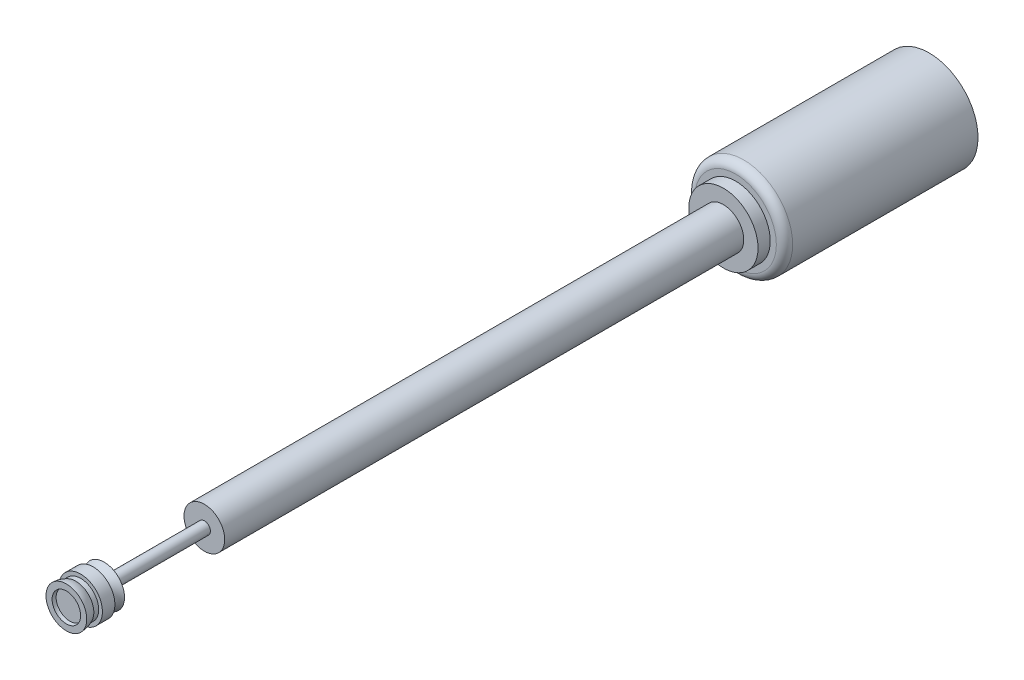
SolidWorks part; units mm, degrees
ref_plane "Front Plane" through (0, 0, 0) normal (0, 0, 1) x (1, 0, 0)
ref_plane "Top Plane" through (0, 0, 0) normal (0, 1, 0) x (1, 0, 0)
ref_plane "Right Plane" through (0, 0, 0) normal (1, 0, 0) x (0, 0, -1)
sketch "Sketch1" plane through (0, 0, 0) normal (0, 0, 1) x (1, 0, 0)
  circle A0 centre (0, 0) radius 0.5
  circle A1 centre (0, 0) radius 1.2
  dimension "D1" = 1
  dimension "D2" = 2.4
extrude "Boss-Extrude2" add sketch "Sketch1" along normal blind 15.5 contours A0
extrude "Boss-Extrude3" add sketch "Sketch1<3>" against normal blind 4.75 separate body contours A0 | A1 A0 region at (0, 0, 0) region at (-1.1661, 0, 0)
sketch "Sketch1<3>" plane through (0, 0, 0) normal (0, 0, 1) x (1, 0, 0) same geometry as "Sketch1"
fillet "Fillet1" radius 0.2 1 edges at (1.2, 0, 0)
sketch "Sketch2" plane through (0, 0, 0) normal (0, 0, 1) x (1, 0, 0)
  circle A0 centre (0, 0) radius 0.85
  dimension "D1" = 1.7
extrude "Boss-Extrude4" add sketch "Sketch2" along normal blind 0.3
sketch "Sketch3" plane through (0, 0, 0) normal (0, 1, 0) x (1, 0, 0)
  line L0 (0.5, -15.5) -> (0, -15.5)
  line L1 (-0.5, -15.5) -> (0.5, -15.5) construction
  line L2 (0, -15.5) -> (0, -16.0775)
  line L3 (0.35, -16.4275) -> (0.5, -16.4275)
  line L4 (0.4436, -16.1968) -> (0.4436, -16.0775)
  line L5 (0.4436, -16.0775) -> (0.5351, -16.0775)
  line L6 (0.5351, -16.0775) -> (0.5351, -15.771)
  line L7 (0.5351, -15.771) -> (0.3881, -15.771)
  arc A0 (0, -16.0775) -> (0.35, -16.4275) centre (0, -16.4275) cw
  arc A1 (0.5, -16.4275) -> (0.4436, -16.1968) centre (0, -16.4275) ccw
  arc A2 (0.3881, -15.771) -> (0.5, -15.5) centre (0.7723, -15.771) cw
  dimension "D2" = 0.35
  dimension "D3" = 0.5
  dimension "D1" = 0.9275
revolve "Revolve1" add sketch "Sketch3" angle 360 about L2
sketch "Sketch4" plane through (0, 0, 0) normal (0, 1, 0) x (1, 0, 0)
  line L0 (0, -16.4275) -> (0, -15.1419) construction
  line L1 (-0.5, -16.4275) -> (0.5, -16.4275) construction
  line L2 (0.5, -15.5) -> (-0.5, -15.5) construction
  line L3 (-0.4522, -16.34) -> (0, -16.34)
  line L4 (-0.4522, -16.34) -> (-0.4522, -16.2888)
  line L5 (-0.4522, -16.2888) -> (0, -16.2888)
  line L6 (0, -16.34) -> (0, -16.2888)
  line L7 (-0.4522, -16.34) -> (0, -16.2888) construction
  line L8 (-0.4522, -16.2888) -> (0, -16.34) construction
  point P5 (0, -16.2888)
  dimension "D1" = 0.84
revolve "Revolve2" add sketch "Sketch4" angle 360 about L6
sketch "Sketch5" plane through (0, 0, 0) normal (0, 1, 0) x (1, 0, 0)
  line L0 (0.5, -15.5) -> (-0.5, -15.5) construction
  line L1 (-0.148, -15.5) -> (-2.4843, -15.5)
  line L2 (-0.148, -15.5) -> (-0.148, -13.04)
  line L3 (-0.148, -13.04) -> (-2.4843, -13.04)
  line L4 (-2.4843, -15.5) -> (-2.4843, -13.04)
  line L5 (0, -16.4275) -> (0, -15.5) construction
  line L6 (-0.5, -16.4275) -> (0.5, -16.4275) construction
  dimension "D1" = 2.46
  dimension "D2" = 0.296
revolve "Cut-Revolve1" cut sketch "Sketch5" angle 360 about L5
sketch "Sketch6" plane through (0, 0, -4.75) normal (0, 0, -1) x (-1, 0, 0)
  point P0 (0, 0)
